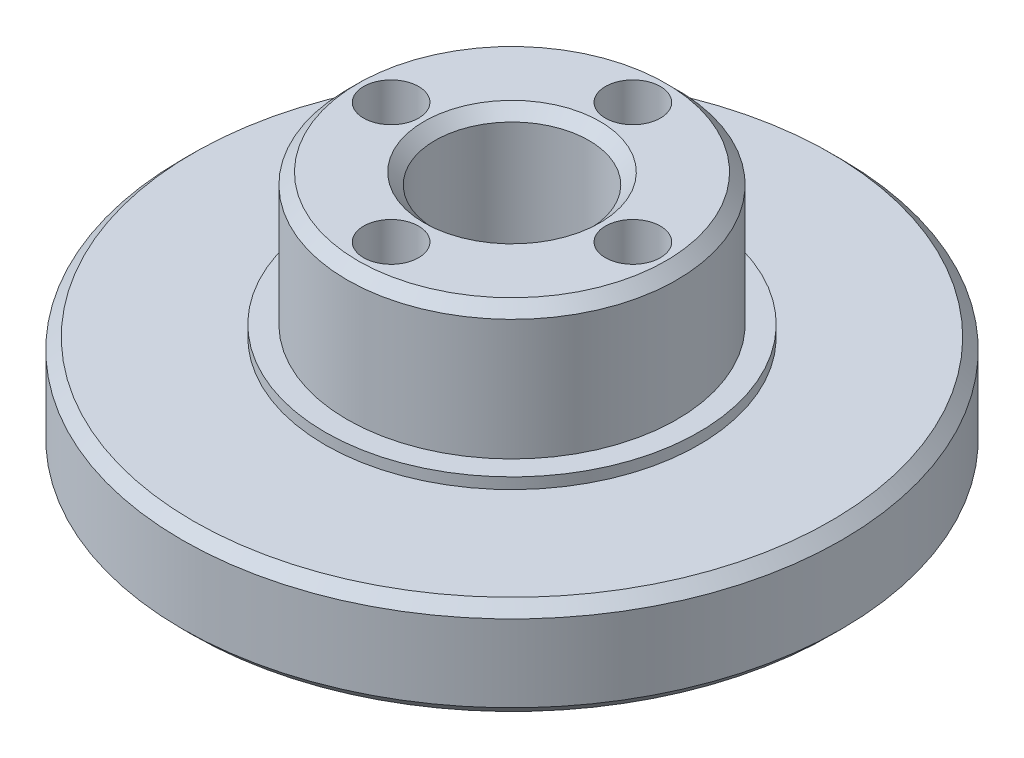
SolidWorks part; units mm, degrees
ref_plane "前视基准面" through (0, 0, 0) normal (0, 0, 1) x (1, 0, 0)
ref_plane "上视基准面" through (0, 0, 0) normal (0, 1, 0) x (1, 0, 0)
ref_plane "右视基准面" through (0, 0, 0) normal (1, 0, 0) x (0, 0, -1)
other "Configuration Table"
sketch "草图1" plane through (0, 0, 0) normal (0, 1, 0) x (1, 0, 0)
  circle A0 centre (0, 0) radius 11.525 construction
  circle A1 centre (0, 11.525) radius 2
  circle A2 centre (9.9809, 5.7625) radius 2
  circle A3 centre (9.9809, -5.7625) radius 2
  circle A4 centre (0, -11.525) radius 2
  circle A5 centre (-9.9809, -5.7625) radius 2
  circle A6 centre (-9.9809, 5.7625) radius 2
  circle A8 centre (0, 0) radius 15
  point P18 (0, 0)
  dimension "D1" = 23.05
  dimension "D2" = 4
  dimension "D5" = 30
  dimension "D3" = 6
extrude "凸台-拉伸1" add sketch "草图1" along normal blind 2.5
sketch "草图2" plane through (0, 2.5, 0) normal (0, 1, 0) x (1, 0, 0)
  circle A0 centre (0, 0) radius 15
extrude "凸台-拉伸2" add sketch "草图2" along normal blind 2
sketch "草图3" plane through (0, 4.5, 0) normal (0, 1, 0) x (1, 0, 0)
  circle A0 centre (0, 0) radius 8.5
  dimension "D1" = 17
extrude "凸台-拉伸3" add sketch "草图3" along normal blind 0.5
sketch "草图4" plane through (0, 5, 0) normal (0, 1, 0) x (1, 0, 0)
  circle A0 centre (0, 0) radius 7.5
  dimension "D1" = 15
extrude "凸台-拉伸4" add sketch "草图4" along normal blind 6
sketch "草图5" plane through (0, 11, 0) normal (0, 1, 0) x (1, 0, 0)
  circle A0 centre (0, 5.5) radius 1.25
  circle A1 centre (5.5, 0) radius 1.25
  circle A2 centre (0, -5.5) radius 1.25
  circle A3 centre (-5.5, 0) radius 1.25
  circle A4 centre (0, 0) radius 3.5
  point P12 (0, 0)
  dimension "D1" = 2.5
  dimension "D2" = 5.5
  dimension "D4" = 7
  dimension "D3" = 4
extrude "切除-拉伸1" cut sketch "草图5" against normal through all
chamfer "倒角1" distance 0.5 angle 45 15 edges at (-9.9809, 0, -3.7625) (-9.9809, 0, 7.7625) (0, 0, 13.525) (9.9809, 0, 7.7625) (9.9809, 0, -3.7625) (0, 0, -9.525) (0, 0, 15) (0, 11, 7.5) (0, 4.5, 15) (0, 0, 3.5) (5.5, 0, 1.25) (0, 0, 6.75) (-5.5, 0, 1.25) (0, 0, -4.25) (0, 11, 3.5)
